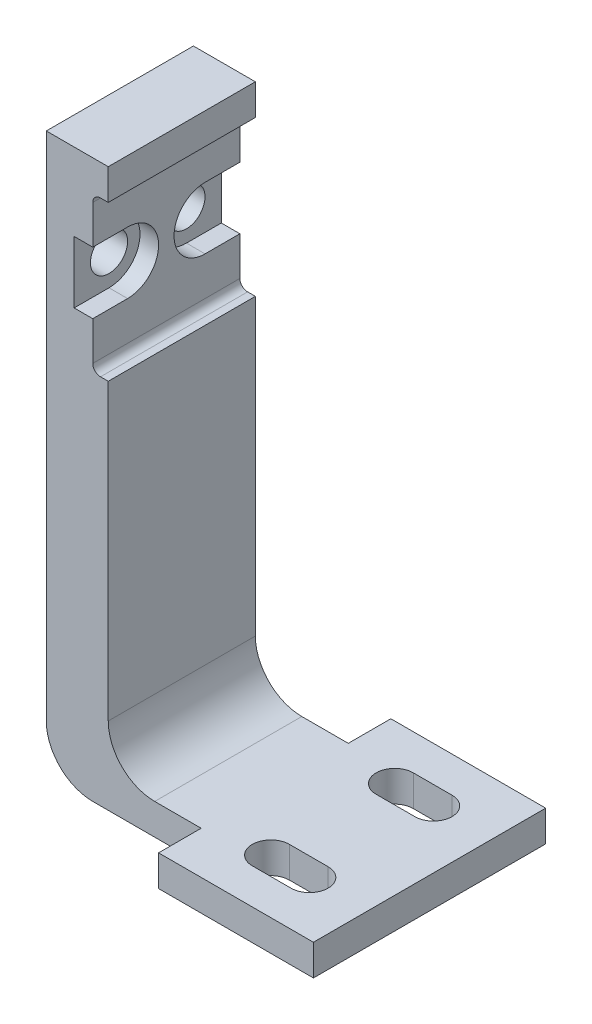
SolidWorks part; units mm, degrees
material "6061-T6 (SS)"
ref_plane "Front Plane" through (0, 0, 0) normal (0, 0, 1) x (1, 0, 0)
ref_plane "Top Plane" through (0, 0, 0) normal (0, 1, 0) x (1, 0, 0)
ref_plane "Right Plane" through (0, 0, 0) normal (1, 0, 0) x (0, 0, -1)
sketch "Sketch1" plane through (0, 0, 0) normal (0, 0, 1) x (1, 0, 0)
  line L0 (-14.4886, 20.89) -> (-16.5374, 20.89) construction
  line L9 (-16.5374, 15.89) -> (-16.5374, 25.89)
  line L10 (-19.5374, 0) -> (-19.5374, 27.89)
  line L11 (-19.5374, 27.89) -> (-15.5374, 27.89)
  line L12 (-15.5374, 27.89) -> (-15.5374, 25.89)
  line L17 (-15.4274, -6.11) -> (0.4626, -6.11)
  line L18 (0.4626, -6.11) -> (0.4626, -8.11)
  line L19 (0.4626, -8.11) -> (-11.4274, -8.11)
  line L20 (-16.5374, 25.89) -> (-15.5374, 25.89)
  line L21 (-16.5374, 15.89) -> (-15.5374, 15.89)
  line L22 (-15.5374, 15.89) -> (-15.5374, 12.89)
  line L23 (-19.5374, 0) -> (-19.5374, -8.11)
  line L24 (-19.5374, -8.11) -> (-11.4274, -8.11)
  line L25 (-15.5374, 12.89) -> (-15.5374, -6.11)
  line L26 (-15.5374, -6.11) -> (-15.4274, -6.11)
  line L29 (-15.4274, -6.11) -> (-13.0144, -6.11) construction
  point P15 (-16.5374, 20.89)
  point P21 (-12.4274, 0)
  dimension "D3" = 36
  dimension "D4" = 3
  dimension "D2" = 4
  dimension "D5" = 20
  dimension "D6" = 10
  dimension "D7" = 2
  dimension "D8" = 1
  dimension "D10" = 2
extrude "Boss-Extrude1" add sketch "Sketch1" along normal mid plane 9.5
sketch "Sketch2" plane through (-16.5374, 0, 0) normal (1, 0, 0) x (0, 0, -1)
  line L0 (-4.75, 20.89) -> (4.75, 20.89) construction
  line L1 (-4.75, 15.89) -> (-4.75, 25.89) construction
  line L2 (4.75, 15.89) -> (4.75, 25.89) construction
  point P8 (-2.5, 20.89)
  point P9 (0, 20.89)
  point P11 (2.5, 20.89)
  dimension "D2" = 2.5
  dimension "D1" = 2.5
hole_wizard "M2 Clearance Hole1" positions "3DSketch1" profile "Sketch3" hole size "M2" standard "ANSI Metric" end condition through all
sketch3d "3DSketch1"
  point P0 (-16.5374, 20.89, 2.5)
  point P3 (-16.5374, 20.89, -2.5)
sketch "Sketch3" plane through (-16.5374, 20.89, 2.5) normal (0, 1, 0) x (0, 0, -1)
  line L0 (0, 0) -> (0, 3)
  line L1 (0, 3) -> (1.2, 3)
  line L2 (1.2, 3) -> (1.2, 0)
  line L5 (1.2, 0) -> (0, 0)
  line L11 (0, -6.35) -> (0, 107.95) construction
  dimension "Thru Hole Dia." = 2.4
  dimension "Thru Hole Depth" = 3
sketch "Sketch4" plane through (-16.5374, 0, 0) normal (1, 0, 0) x (0, 0, -1)
  line L0 (-2.5, 22.89) -> (-4.75, 22.89)
  line L1 (-4.75, 15.89) -> (-4.75, 25.89) construction
  line L2 (-4.75, 22.89) -> (-4.75, 18.89)
  line L3 (-4.75, 18.89) -> (-2.5, 18.89)
  line L4 (0, 55) -> (0, -55) construction
  line L5 (4.75, 18.89) -> (2.5, 18.89)
  line L6 (4.75, 22.89) -> (4.75, 18.89)
  line L7 (2.5, 22.89) -> (4.75, 22.89)
  arc A0 (-2.5, 18.89) -> (-2.5, 22.89) centre (-2.5, 20.89) ccw
  arc A1 (2.5, 22.89) -> (2.5, 18.89) centre (2.5, 20.89) ccw
  dimension "D1" = 4
  dimension "D2" = 4
extrude "Cut-Extrude1" cut sketch "Sketch4" against normal blind 1.2
sketch "Sketch5" plane through (0, -8.11, 0) normal (0, -1, 0) x (1, 0, 0)
  line L0 (0.4626, -7.5) -> (0.4626, 7.5)
  line L1 (0.4626, 4.75) -> (0.4626, -4.75) construction
  line L2 (0.4626, 7.5) -> (-9.5374, 7.5)
  line L3 (-9.5374, 7.5) -> (-9.5374, -7.5)
  line L4 (-9.5374, -7.5) -> (0.4626, -7.5)
  point P3 (0.4626, 0)
  dimension "D1" = 10
  dimension "D2" = 15
extrude "Boss-Extrude2" add sketch "Sketch5" against normal blind 2
sketch "Sketch6" plane through (0, -6.11, 0) normal (0, 1, 0) x (1, 0, 0)
  line L0 (0.4626, 0) -> (-9.5374, 0) construction
  line L1 (0.4626, 7.5) -> (0.4626, -7.5) construction
  line L2 (-3.2874, -4) -> (-5.7874, -4) construction
  line L3 (-4.5374, -7.5) -> (-4.5374, 7.5) construction
  line L4 (0.4626, -7.5) -> (-9.5374, -7.5) construction
  line L5 (-9.5374, 7.5) -> (0.4626, 7.5) construction
  line L6 (-3.2874, -5.2) -> (-5.7874, -5.2)
  line L7 (-3.2874, -2.8) -> (-5.7874, -2.8)
  line L8 (-3.2874, 4) -> (-5.7874, 4) construction
  line L9 (-3.2874, 5.2) -> (-5.7874, 5.2)
  line L10 (-3.2874, 2.8) -> (-5.7874, 2.8)
  arc A0 (-3.2874, -5.2) -> (-3.2874, -2.8) centre (-3.2874, -4) ccw
  arc A1 (-5.7874, -2.8) -> (-5.7874, -5.2) centre (-5.7874, -4) ccw
  arc A2 (-3.2874, 5.2) -> (-3.2874, 2.8) centre (-3.2874, 4) cw
  arc A3 (-5.7874, 2.8) -> (-5.7874, 5.2) centre (-5.7874, 4) cw
  point P12 (-4.5374, -4)
  point P13 (-4.5374, 0)
  point P14 (-4.5374, 4)
  point P15 (-4.5374, -4)
  point P23 (-4.5374, 4)
  dimension "D3" = 1.2
  dimension "D1" = 4
  dimension "D2" = 2.5
extrude "Cut-Extrude2" cut sketch "Sketch6" against normal up to surface (2 mm away) up to face at (-9.5374, -8.11, 0)
fillet "Fillet1" radius 3 2 edges at (-15.5374, -6.11, 0) (-19.5374, -8.11, 0)
fillet "Fillet2" radius 0.5 2 edges at (-16.5374, 15.89, 0) (-16.5374, 25.89, 0)
